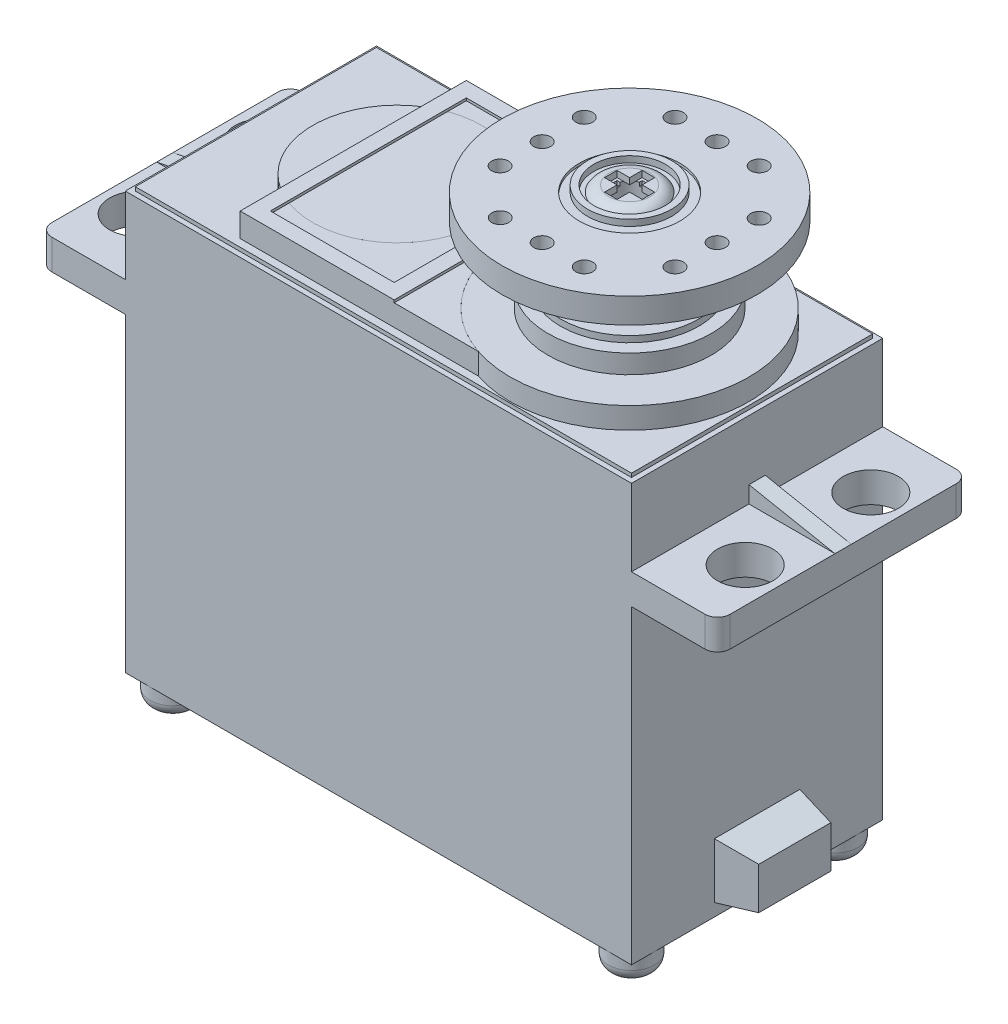
SolidWorks part; units mm, degrees
ref_plane "Alzado" through (0, 0, 0) normal (0, 0, 1) x (1, 0, 0)
ref_plane "Planta" through (0, 0, 0) normal (0, 1, 0) x (1, 0, 0)
ref_plane "Vista lateral" through (0, 0, 0) normal (1, 0, 0) x (0, 0, -1)
sketch "Croquis1" plane through (0, 0, 0) normal (0, 1, 0) x (1, 0, 0)
  line L1 (-20.15, 10) -> (20.15, 10)
  line L2 (-20.15, 10) -> (-20.15, -10)
  line L3 (-20.15, -10) -> (20.15, -10)
  line L4 (20.15, 10) -> (20.15, -10)
  line L5 (-20.15, 10) -> (20.15, -10) construction
  line L6 (-20.15, -10) -> (20.15, 10) construction
  point P0 (0, 0)
  dimension "D1" = 40.3
  dimension "D2" = 20
extrude "Saliente-Extruir1" add sketch "Croquis1" along normal blind 35.5
sketch "Croquis2" plane through (20.15, 0, 0) normal (1, 0, 0) x (0, 0, -1)
  line L0 (10, 35.5) -> (10, 26.7) construction
  line L1 (10, 35.5) -> (10, 0) construction
  line L2 (10, 26.7) -> (10, 29.1)
  line L3 (10, 29.1) -> (-10, 29.1)
  line L4 (-10, 35.5) -> (-10, 0) construction
  line L5 (-10, 29.1) -> (-10, 26.7)
  line L6 (-10, 26.7) -> (10, 26.7)
  dimension "D1" = 8.8
  dimension "D2" = 2.4
extrude "Saliente-Extruir2" add sketch "Croquis2" along normal blind 6.85
sketch "Croquis3" plane through (-20.15, 0, 0) normal (-1, 0, 0) x (0, 0, 1)
  line L0 (10, 35.5) -> (10, 26.7) construction
  line L1 (10, 35.5) -> (10, 0) construction
  line L2 (10, 26.7) -> (10, 29.1)
  line L3 (10, 29.1) -> (-10, 29.1)
  line L4 (-10, 35.5) -> (-10, 0) construction
  line L5 (-10, 29.1) -> (-10, 26.7)
  line L6 (-10, 26.7) -> (10, 26.7)
  dimension "D1" = 8.8
  dimension "D2" = 2.4
extrude "Saliente-Extruir3" add sketch "Croquis3" along normal blind 6.85
fillet "Redondeo1" radius 1 1 edges at (27, 27.9, 10) type face fillet first side face at (27, 27.9, 0) second side face at (0, 27.275, 10)
fillet "Redondeo2" radius 1 1 edges at (27, 27.9, -10) type face fillet first side face at (27, 27.9, -0.5) second side face at (0, 27.275, -10)
fillet "Redondeo3" radius 1 1 edges at (-27, 27.9, 10) type face fillet first side face at (-27, 27.9, 0) second side face at (-0.25, 27.275, 10)
fillet "Redondeo4" radius 1 1 edges at (-27, 27.9, -10) type face fillet first side face at (-27, 27.9, -0.5) second side face at (-0.25, 27.275, -10)
sketch "Croquis4" plane through (0, 29.1, 0) normal (0, 1, 0) x (1, 0, 0)
  line L0 (27, 0) -> (20.15, 0) construction
  line L1 (27, 9) -> (27, -9) construction
  line L2 (20.15, 10) -> (20.15, -10) construction
  line L3 (20.15, 0) -> (20.15, 0.65)
  line L4 (20.15, -10) -> (20.15, 10) construction
  line L5 (20.15, 0.65) -> (27, 0.65)
  line L6 (27, 0.65) -> (27, 0)
  line L7 (27, 0) -> (27, -0.65)
  line L8 (27, -0.65) -> (20.15, -0.65)
  line L9 (20.15, -0.65) -> (20.15, 0)
  dimension "D1" = 0.65
  dimension "D2" = 0.65
extrude "Saliente-Extruir4" add sketch "Croquis4" along normal blind 1.5
chamfer "Chaflán1" distance 1.5 angle 79 1 edges at (27, 30.6, 0) first distance on face at (27, 28.875, 0)
sketch "Croquis5" plane through (0, 29.1, 0) normal (0, 1, 0) x (1, 0, 0)
  line L0 (-27, 0) -> (-20.15, 0) construction
  line L1 (-27, -9) -> (-27, 9) construction
  line L2 (-20.15, 10) -> (-20.15, -10) construction
  line L3 (-27, 0) -> (-27, 0.65)
  line L4 (-27, 0.65) -> (-20.15, 0.65)
  line L5 (-20.15, -10) -> (-20.15, 10) construction
  line L6 (-20.15, 0.65) -> (-20.15, 0)
  line L7 (-20.15, 0) -> (-20.15, -0.65)
  line L8 (-20.15, -0.65) -> (-27, -0.65)
  line L9 (-27, -0.65) -> (-27, 0)
  dimension "D1" = 0.65
  dimension "D2" = 0.65
extrude "Saliente-Extruir5" add sketch "Croquis5" along normal blind 1.5
chamfer "Chaflán2" distance 1.5 angle 79 1 edges at (-27, 30.6, 0) first distance on face at (-27, 28.875, 0)
sketch "Croquis6" plane through (0, 29.1, 0) normal (0, 1, 0) x (1, 0, 0)
  line L0 (27, 0) -> (20.15, 0) construction
  line L1 (27, 0.65) -> (27, -0.65) construction
  line L2 (20.15, -10) -> (20.15, 10) construction
  line L3 (27.75, 10) -> (24.2, 10) construction
  line L4 (26, 10) -> (20.15, 10) construction
  line L5 (24.2, 10) -> (24.2, 5) construction
  line L6 (24.2, 5) -> (24.2, -5) construction
  line L7 (24.2, -5) -> (24.2, -10) construction
  line L8 (26, -10) -> (20.15, -10) construction
  line L9 (24.2, -10) -> (27.75, -10) construction
  circle A0 centre (24.2, 5) radius 2.2
  circle A1 centre (24.2, -5) radius 2.2
  dimension "D1" = 5
  dimension "D3" = 4.4
  dimension "D5" = 4.4
  dimension "D2" = 3.55
  dimension "D4" = 10
  dimension "D6" = 5
extrude "Cortar-Extruir1" cut sketch "Croquis6" against normal blind 2.6
sketch "Croquis7" plane through (0, 29.1, 0) normal (0, 1, 0) x (1, 0, 0)
  line L0 (-24.2, -10) -> (-27.75, -10) construction
  line L1 (-26, -10) -> (-20.15, -10) construction
  line L2 (-24.2, -10) -> (-24.2, -5) construction
  line L3 (-24.2, -5) -> (-24.2, 5) construction
  line L4 (-24.2, 5) -> (-24.2, 10) construction
  line L5 (-26, 10) -> (-20.15, 10) construction
  circle A0 centre (-24.2, -5) radius 2.2
  circle A1 centre (-24.2, 5) radius 2.2
  dimension "D3" = 4.4
  dimension "D4" = 10
  dimension "D6" = 4.4
  dimension "D1" = 5
  dimension "D2" = 3.55
  dimension "D5" = 5
extrude "Cortar-Extruir2" cut sketch "Croquis7" against normal blind 2.6
sketch "Croquis8" plane through (0, 35.5, 0) normal (0, 1, 0) x (1, 0, 0)
  line L0 (-20.15, 10) -> (-20.15, 9.6) construction
  line L1 (-20.15, 10) -> (-20.15, -10) construction
  line L2 (-20.15, 9.6) -> (-19.75, 9.6) construction
  line L3 (-20.15, -10) -> (-20.15, -9.6) construction
  line L4 (-20.15, -9.6) -> (-19.75, -9.6) construction
  line L5 (20.15, -9.6) -> (19.75, -9.6) construction
  line L6 (20.15, -10) -> (20.15, 10) construction
  line L7 (19.75, -9.6) -> (19.75, -10) construction
  line L8 (-20.15, -10) -> (20.15, -10) construction
  line L9 (20.15, 10) -> (20.15, 9.6) construction
  line L10 (20.15, 9.6) -> (19.75, 9.6) construction
  line L11 (19.75, 9.6) -> (19.75, 10) construction
  line L12 (20.15, 10) -> (-20.15, 10) construction
  line L13 (-20.15, 10) -> (-20.15, -10)
  line L14 (-20.15, -10) -> (20.15, -10)
  line L15 (20.15, -10) -> (20.15, 10)
  line L16 (20.15, 10) -> (-20.15, 10)
  line L17 (-19.75, 9.6) -> (-19.75, -9.6)
  line L18 (-19.75, -9.6) -> (19.75, -9.6)
  line L19 (19.75, -9.6) -> (19.75, 9.6)
  line L20 (19.75, 9.6) -> (-19.75, 9.6)
  dimension "D1" = 0.4
  dimension "D2" = 0.4
  dimension "D3" = 0.4
  dimension "D4" = 0.4
  dimension "D5" = 0.4
extrude "Cortar-Extruir3" cut sketch "Croquis8" against normal blind 0.3
sketch "Croquis9" plane through (0, 0, 0) normal (0, -1, 0) x (1, 0, 0)
  line L0 (-20.15, -10) -> (-16.35, -10)
  line L1 (-20.15, -10) -> (-20.15, -6.2)
  line L2 (-16.35, -10) -> (-16.35, -6.2)
  line L3 (-20.15, -6.2) -> (-16.35, -6.2)
  line L4 (20.15, -10) -> (-20.15, -10) construction
  line L5 (-20.15, 10) -> (-16.35, 10)
  line L6 (-20.15, 10) -> (-20.15, 6.2)
  line L7 (-16.35, 10) -> (-16.35, 6.2)
  line L8 (-20.15, 6.2) -> (-16.35, 6.2)
  line L9 (-20.15, 10) -> (20.15, 10) construction
  line L10 (20.15, 10) -> (20.15, 6.2)
  line L11 (20.15, 10) -> (16.35, 10)
  line L12 (20.15, 6.2) -> (16.35, 6.2)
  line L13 (16.35, 10) -> (16.35, 6.2)
  line L14 (20.15, 10) -> (20.15, -10) construction
  line L15 (20.15, -10) -> (20.15, -6.2)
  line L16 (20.15, -10) -> (16.35, -10)
  line L17 (20.15, -6.2) -> (16.35, -6.2)
  line L18 (16.35, -10) -> (16.35, -6.2)
  line L19 (20.15, 10) -> (20.15, -10) construction
  dimension "D1" = 3.8
  dimension "D2" = 3.8
  dimension "D3" = 3.8
  dimension "D4" = 3.8
  dimension "D5" = 3.8
  dimension "D6" = 3.8
  dimension "D7" = 3.8
  dimension "D8" = 3.8
extrude "Cortar-Extruir4" cut sketch "Croquis9" against normal blind 2
fillet "Redondeo5" radius 2 1 edges at (-16.35, 1, -6.2) type face fillet first side face at (-18.25, 1, -6.2) second side face at (-16.35, 1, -8.1)
fillet "Redondeo6" radius 2 1 edges at (-16.35, 1, 6.2) type face fillet first side face at (-16.35, 1, 8.1) second side face at (-18.25, 1, 6.2)
fillet "Redondeo7" radius 2 1 edges at (16.35, 1, 6.2) type face fillet first side face at (16.35, 1, 8.1) second side face at (18.25, 1, 6.2)
fillet "Redondeo8" radius 2 1 edges at (16.35, 1, -6.2) type face fillet first side face at (18.25, 1, -6.2) second side face at (16.35, 1, -8.1)
sketch "Croquis10" plane through (0, 2, 0) normal (0, -1, 0) x (1, 0, 0)
  line L0 (-20.15, -8.1) -> (20.15, -8.1) construction
  line L2 (-18.25, 10) -> (-18.25, -10) construction
  line L3 (-20.15, -6.2) -> (-20.15, -10) construction
  line L4 (20.15, 10) -> (20.15, -10) construction
  line L5 (-20.15, 8.1) -> (20.15, 8.1) construction
  line L6 (-20.15, 10) -> (-20.15, 6.2) construction
  line L7 (20.15, 6.2) -> (20.15, 10) construction
  line L8 (-16.35, 10) -> (-20.15, 10) construction
  line L9 (-20.15, -10) -> (-16.35, -10) construction
  line L10 (18.25, 10) -> (18.25, -10) construction
  line L11 (20.15, 10) -> (16.35, 10) construction
  line L12 (16.35, -10) -> (20.15, -10) construction
  line L13 (-18.25, 10) -> (-20.15, 10) construction
  line L14 (-20.15, 10) -> (-20.15, 8.1) construction
  line L15 (-20.15, 8.1) -> (-18.25, 8.1) construction
  line L16 (-20.15, -8.1) -> (-20.15, -10) construction
  line L17 (-20.15, -10) -> (-18.25, -10) construction
  line L18 (-18.25, -10) -> (-18.25, -8.1) construction
  line L19 (-18.25, -8.1) -> (-20.15, -8.1) construction
  line L20 (20.15, -8.1) -> (20.15, -10) construction
  line L21 (20.15, -10) -> (18.25, -10) construction
  line L22 (18.25, -10) -> (18.25, -8.1) construction
  line L23 (18.25, -8.1) -> (20.15, -8.1) construction
  line L24 (18.25, 10) -> (20.15, 10) construction
  line L25 (20.15, 10) -> (20.15, 8.1) construction
  line L26 (20.15, 8.1) -> (18.25, 8.1) construction
  line L27 (18.25, 8.1) -> (18.25, 10) construction
  circle A0 centre (-18.25, 8.1) radius 1.825
  circle A1 centre (-18.25, -8.1) radius 1.825
  circle A2 centre (18.25, -8.1) radius 1.825
  circle A3 centre (18.25, 8.1) radius 1.825
  dimension "D1" = 3.65
  dimension "D2" = 3.65
  dimension "D3" = 3.65
  dimension "D4" = 3.65
extrude "Saliente-Extruir6" add sketch "Croquis10" along normal blind 2
fillet "Redondeo9" radius 1 1 edges at (-18.25, 0, -9.925)
fillet "Redondeo10" radius 1 1 edges at (-18.25, 0, 6.275)
fillet "Redondeo11" radius 1 1 edges at (18.25, 0, -9.925)
fillet "Redondeo12" radius 1 1 edges at (18.25, 0, 6.275)
sketch "Croquis11" plane through (0, 0, 0) normal (0, -1, 0) x (1, 0, 0)
  line L0 (-18.25, -10) -> (-18.25, -8.1) construction
  line L1 (-20.15, -10) -> (-16.35, -10) construction
  line L2 (-18.25, -8.1) -> (-20.15, -8.1) construction
  line L3 (-20.15, -6.2) -> (-20.15, -10) construction
  line L4 (-18.25, 8.1) -> (-20.075, 8.1) construction
  line L5 (-18.75, -9.35) -> (-17.75, -9.35)
  line L6 (-18.75, -9.35) -> (-18.75, -8.6)
  line L7 (-18.75, -6.85) -> (-17.75, -6.85)
  line L8 (-17.75, -9.35) -> (-17.75, -8.6)
  line L9 (-18.75, -9.35) -> (-17.75, -6.85) construction
  line L10 (-18.75, -6.85) -> (-17.75, -9.35) construction
  line L11 (-19.5, -8.6) -> (-18.75, -8.6)
  line L12 (-19.5, -8.6) -> (-19.5, -7.6)
  line L13 (-19.5, -7.6) -> (-18.75, -7.6)
  line L14 (-17, -8.6) -> (-17, -7.6)
  line L15 (-19.5, -8.6) -> (-17, -7.6) construction
  line L16 (-19.5, -7.6) -> (-17, -8.6) construction
  line L17 (18.25, 8.1) -> (20.075, 8.1) construction
  line L18 (-18.75, 9.35) -> (-17.75, 9.35)
  line L19 (-18.75, 9.35) -> (-18.75, 8.6)
  line L20 (-18.75, 6.85) -> (-17.75, 6.85)
  line L21 (-17.75, 9.35) -> (-17.75, 8.6)
  line L22 (-18.75, 9.35) -> (-17.75, 6.85) construction
  line L23 (-18.75, 6.85) -> (-17.75, 9.35) construction
  line L24 (-17, 7.6) -> (-17.75, 7.6)
  line L25 (-17, 7.6) -> (-17, 8.6)
  line L26 (-17, 8.6) -> (-17.75, 8.6)
  line L27 (-19.5, 7.6) -> (-19.5, 8.6)
  line L28 (-17, 7.6) -> (-19.5, 8.6) construction
  line L29 (-17, 8.6) -> (-19.5, 7.6) construction
  line L30 (18.25, -8.1) -> (20.075, -8.1) construction
  line L31 (18.75, 6.85) -> (17.75, 6.85)
  line L32 (18.75, 6.85) -> (18.75, 7.6)
  line L33 (18.75, 9.35) -> (17.75, 9.35)
  line L34 (17.75, 6.85) -> (17.75, 7.6)
  line L35 (18.75, 6.85) -> (17.75, 9.35) construction
  line L36 (18.75, 9.35) -> (17.75, 6.85) construction
  line L37 (19.5, 7.6) -> (18.75, 7.6)
  line L38 (19.5, 7.6) -> (19.5, 8.6)
  line L39 (19.5, 8.6) -> (18.75, 8.6)
  line L40 (17, 7.6) -> (17, 8.6)
  line L41 (19.5, 7.6) -> (17, 8.6) construction
  line L42 (19.5, 8.6) -> (17, 7.6) construction
  line L43 (-17.75, -7.6) -> (-17, -7.6)
  line L44 (18.75, -6.85) -> (17.75, -6.85)
  line L45 (18.75, -6.85) -> (18.75, -7.6)
  line L46 (18.75, -9.35) -> (17.75, -9.35)
  line L47 (17.75, -6.85) -> (17.75, -7.6)
  line L48 (18.75, -6.85) -> (17.75, -9.35) construction
  line L49 (18.75, -9.35) -> (17.75, -6.85) construction
  line L50 (17, -8.6) -> (17.75, -8.6)
  line L51 (17, -8.6) -> (17, -7.6)
  line L52 (17, -7.6) -> (17.75, -7.6)
  line L53 (19.5, -8.6) -> (19.5, -7.6)
  line L54 (17, -8.6) -> (19.5, -7.6) construction
  line L55 (17, -7.6) -> (19.5, -8.6) construction
  line L56 (-18.75, -7.6) -> (-18.75, -6.85)
  line L57 (-18.75, 8.6) -> (-19.5, 8.6)
  line L58 (-17.75, -7.6) -> (-17.75, -6.85)
  line L59 (-17.75, -8.6) -> (-17, -8.6)
  line L60 (-17.75, 7.6) -> (-17.75, 6.85)
  line L61 (-18.75, 7.6) -> (-19.5, 7.6)
  line L62 (-18.75, 7.6) -> (-18.75, 6.85)
  line L63 (17.75, 8.6) -> (17, 8.6)
  line L64 (18.75, 8.6) -> (18.75, 9.35)
  line L65 (17.75, 7.6) -> (17, 7.6)
  line L66 (17.75, 8.6) -> (17.75, 9.35)
  line L67 (18.75, -7.6) -> (19.5, -7.6)
  line L68 (18.75, -8.6) -> (18.75, -9.35)
  line L69 (18.75, -8.6) -> (19.5, -8.6)
  line L70 (17.75, -8.6) -> (17.75, -9.35)
  circle A0 centre (-18.25, 8.1) radius 1.825 construction
  circle A1 centre (18.25, 8.1) radius 1.825 construction
  circle A2 centre (18.25, -8.1) radius 1.825 construction
  dimension "D1" = 2.5
  dimension "D2" = 2.5
  dimension "D3" = 1
  dimension "D4" = 1
  dimension "D5" = 1
  dimension "D6" = 1
  dimension "D7" = 2.5
  dimension "D8" = 2.5
  dimension "D9" = 1
  dimension "D10" = 1
  dimension "D11" = 2.5
  dimension "D12" = 2.5
  dimension "D13" = 1
  dimension "D14" = 1
  dimension "D15" = 2.5
  dimension "D16" = 2.5
extrude "Cortar-Extruir5" cut sketch "Croquis11" against normal blind 1
chamfer "Chaflán3" distance 2 angle 45 1 edges at (0, 0, -10)
chamfer "Chaflán4" distance 2 angle 45 1 edges at (20.15, 0, 0)
chamfer "Chaflán5" distance 2 angle 45 1 edges at (0, 0, 10)
chamfer "Chaflán6" distance 2 angle 45 1 edges at (-20.15, 0, 0)
sketch "Croquis12" plane through (0, 35.2, 0) normal (0, 1, 0) x (1, 0, 0)
  line L0 (0, 9.6) -> (0, 9) construction
  line L1 (0, 9) -> (-12, 9)
  line L2 (-12, 9) -> (-12, -9)
  line L3 (-12, -9) -> (0, -9)
  line L7 (19.75, 9.6) -> (-19.75, 9.6) construction
  line L8 (19.75, 0) -> (19.15, 0) construction
  line L11 (19.75, -9.6) -> (19.75, 9.6) construction
  line L12 (0, -9.6) -> (0, -9) construction
  line L13 (-19.75, -9.6) -> (19.75, -9.6) construction
  line L14 (-19.75, 0) -> (-19.15, 0) construction
  line L15 (-19.75, 9.6) -> (-19.75, -9.6) construction
  line L16 (0, 9) -> (19.15, 9) construction
  line L17 (19.15, 9) -> (19.15, 0) construction
  line L18 (19.15, 0) -> (19.15, -9) construction
  line L19 (19.15, -9) -> (0, -9) construction
  line L20 (0, -9) -> (-19.15, -9) construction
  line L22 (-19.15, -9) -> (-19.15, 0) construction
  line L23 (-19.15, 0) -> (-19.15, 9) construction
  line L24 (-19.15, 9) -> (0, 9) construction
  line L25 (0, -9) -> (10, -9)
  line L26 (10, -9) -> (10, 9)
  line L27 (10, 9) -> (0, 9)
  dimension "D3" = 0.6
  dimension "D1" = 0.6
  dimension "D5" = 10
  dimension "D2" = 0.6
  dimension "D4" = 0.6
  dimension "D6" = 12
extrude "Saliente-Extruir7" add sketch "Croquis12" along normal blind 2.0001
sketch "Croquis13" plane through (0, 37.2001, 0) normal (0, 1, 0) x (1, 0, 0)
  line L0 (20.15, 0) -> (10, 0) construction
  line L1 (20.15, -0.65) -> (20.15, 0.65) construction
  circle A0 centre (10, 0) radius 9.5
  dimension "D2" = 19
  dimension "D1" = 10.15
extrude "Saliente-Extruir8" add sketch "Croquis13" along normal blind 0.0001 and the other way blind 2
sketch "Croquis14" plane through (0, 37.2002, 0) normal (0, 1, 0) x (1, 0, 0)
  circle A0 centre (10, 0) radius 6.5
  dimension "D1" = 13
extrude "Saliente-Extruir9" add sketch "Croquis14" along normal blind 1.5
sketch "Croquis15" plane through (0, 38.7002, 0) normal (0, 1, 0) x (1, 0, 0)
  circle A0 centre (10, 0) radius 5.5
  dimension "D1" = 11
extrude "Saliente-Extruir10" add sketch "Croquis15" along normal blind 0.5
sketch "Croquis16" plane through (0, 39.2002, 0) normal (0, 1, 0) x (1, 0, 0)
  circle A0 centre (10, 0) radius 2.9
extrude "Saliente-Extruir11" add sketch "Croquis16" along normal blind 4
sketch "Croquis17" plane through (0, 43.2002, 0) normal (0, 1, 0) x (1, 0, 0)
  circle A0 centre (10, 0) radius 0.85
  dimension "D1" = 1.7
extrude "Cortar-Extruir6" cut sketch "Croquis17" against normal blind 4
sketch "Croquis18" plane through (20.15, 0, 0) normal (1, 0, 0) x (0, 0, -1)
  line L0 (0, 2) -> (0, 3) construction
  line L1 (-6.2, 2) -> (6.2, 2) construction
  line L2 (0, 3) -> (0, 5.2) construction
  line L4 (-3.4, 7.4) -> (3.4, 7.4)
  line L5 (-3.4, 7.4) -> (-3.4, 3)
  line L6 (-3.4, 3) -> (3.4, 3)
  line L7 (3.4, 7.4) -> (3.4, 3)
  line L8 (-3.4, 7.4) -> (3.4, 3) construction
  line L9 (-3.4, 3) -> (3.4, 7.4) construction
  dimension "D1" = 1
  dimension "D2" = 2.2
  dimension "D3" = 4.4
  dimension "D4" = 6.8
extrude "Saliente-Extruir12" add sketch "Croquis18" along normal blind 3
chamfer "Chaflán7" distance 3 angle 10 1 edges at (23.15, 7.4, 0) first distance on face at (21.65, 7.4, 0)
chamfer "Chaflán8" distance 3 angle 10 1 edges at (23.15, 3, 0) first distance on face at (21.65, 3, 0)
chamfer "Chaflán9" distance 3 angle 10 1 edges at (23.15, 5.2, -3.4) first distance on face at (21.65, 5.2, -3.4)
chamfer "Chaflán10" distance 3 angle 10 1 edges at (23.15, 5.2, 3.4) first distance on face at (21.65, 5.2, 3.4)
sketch "Croquis19" plane through (0, 37.2001, 0) normal (0, 1, 0) x (1, 0, 0)
  line L0 (-12, 0) -> (-8.5, 0) construction
  line L1 (-12, 9) -> (-12, -9) construction
  circle A0 centre (-8.5, 0) radius 6.7149
  dimension "D1" = 3.5
extrude "Saliente-Extruir13" add sketch "Croquis19" along normal blind 0.0001 and the other way blind 2
sketch "Croquis20" plane through (0, 37.2001, 0) normal (0, 1, 0) x (1, 0, 0)
  line L0 (0.2582, -7.8) -> (0.2582, -9)
  line L1 (-12, -9) -> (6.9586, -9) construction
  line L3 (6.9586, 9) -> (-12, 9) construction
  line L4 (-0.9418, 7.8) -> (-0.9418, -7.8)
  line L6 (-12, -9) -> (-12, -5.7306) construction
  line L8 (-12, 5.7306) -> (-12, 9) construction
  line L9 (-0.9418, 7.8) -> (-10.8, 7.8)
  line L10 (-10.8, 7.8) -> (-10.8, -7.8)
  line L11 (-10.8, -7.8) -> (-0.9418, -7.8)
  line L14 (-0.9418, 9) -> (0.2582, 9)
  line L15 (0.2582, 9) -> (0.2582, 7.8)
  line L16 (0.2582, 7.8) -> (0.2582, -7.8)
  line L17 (0.2582, -9) -> (-0.9418, -9)
  line L18 (-0.9418, -9) -> (-12, -9)
  line L19 (-12, -9) -> (-12, -7.8)
  line L20 (-12, -7.8) -> (-12, 7.8)
  line L21 (-12, 7.8) -> (-12, 9)
  line L22 (-12, 9) -> (-0.9418, 9)
extrude "Saliente-Extruir14" add sketch "Croquis20" along normal blind 0.2
sketch "Croquis21" plane through (0, 43.2002, 0) normal (0, 1, 0) x (1, 0, 0)
  circle A0 centre (10, 0) radius 4.3
  dimension "D1" = 8.6
extrude "Saliente-Extruir15" add sketch "Croquis21" along normal blind 2 and the other way blind 3
sketch "Croquis22" plane through (0, 45.2002, 0) normal (0, 1, 0) x (1, 0, 0)
  circle A0 centre (10, 0) radius 10.15
  dimension "D1" = 20.3
extrude "Saliente-Extruir16" add sketch "Croquis22" along normal blind 0.0001 and the other way blind 2
sketch "Croquis23" plane through (0, 45.2003, 0) normal (0, 1, 0) x (1, 0, 0)
  circle A0 centre (10, 0) radius 1.375
  dimension "D1" = 2.75
extrude "Cortar-Extruir7" cut sketch "Croquis23" against normal blind 5.2
sketch "Croquis24" plane through (0, 45.2003, 0) normal (0, 1, 0) x (1, 0, 0)
  circle A0 centre (10, 0) radius 2.85
  circle A1 centre (10, 0) radius 3.35
  dimension "D1" = 5.7
  dimension "D2" = 6.7
extrude "Saliente-Extruir17" add sketch "Croquis24" along normal blind 0.5
chamfer "Chaflán11" distance 0.75 angle 45 1 edges at (10, 40.2002, 4.3)
sketch "Croquis25" plane through (0, 45.2003, 0) normal (0, 1, 0) x (1, 0, 0)
  circle A0 centre (10, 0) radius 2.5
  dimension "D1" = 5
extrude "Saliente-Extruir18" add sketch "Croquis25" along normal blind 0.5
fillet "Redondeo13" radius 1 1 edges at (10, 45.7003, 2.5)
sketch "Croquis27" plane through (0, 45.7003, 0) normal (0, 1, 0) x (1, 0, 0)
  line L1 (9.5, -1.5) -> (10.5, -1.5)
  line L2 (9.5, -1.5) -> (9.5, 1.5)
  line L3 (9.5, 1.5) -> (10.5, 1.5)
  line L4 (10.5, -1.5) -> (10.5, 1.5)
  line L5 (9.5, -1.5) -> (10.5, 1.5) construction
  line L6 (9.5, 1.5) -> (10.5, -1.5) construction
  line L7 (8.5, 0.5) -> (11.5, 0.5)
  line L8 (8.5, 0.5) -> (8.5, -0.5)
  line L9 (8.5, -0.5) -> (11.5, -0.5)
  line L10 (11.5, 0.5) -> (11.5, -0.5)
  line L11 (8.5, 0.5) -> (11.5, -0.5) construction
  line L12 (8.5, -0.5) -> (11.5, 0.5) construction
  point P0 (10, 0)
  point P6 (10, 0)
  dimension "D1" = 3
  dimension "D2" = 3
  dimension "D3" = 1
  dimension "D4" = 1
extrude "Cortar-Extruir8" cut sketch "Croquis27" against normal blind 1 contours L2 L7 L4 L3 | L2 L9 L4 L7 | L9 L2 L1 L4 | L8 L9 L2 L7 | L10 L7 L4 L9 region at (10, 45.7003, 1) region at (9, 45.7003, 0) region at (10, 45.7003, 0) region at (11, 45.7003, 0) region at (10, 45.7003, -1)
sketch "Croquis28" plane through (0, 45.2003, 0) normal (0, 1, 0) x (1, 0, 0)
  circle A0 centre (10, 0) radius 4
extrude "Cortar-Extruir10" cut sketch "Croquis28" against normal blind 0.2
sketch "Croquis29" plane through (0, 45.2003, 0) normal (0, 1, 0) x (1, 0, 0)
  line L0 (10, 0) -> (10, 6.9625) construction
  line L1 (10, 0) -> (16.9625, 0) construction
  line L2 (10, 0) -> (10, -6.9625) construction
  line L3 (10, -10.15) -> (10.0213, -10.1229) construction
  line L4 (10, 0) -> (3.0375, 0) construction
  circle A0 centre (10, 0) radius 10.15 construction
  circle A1 centre (3.0375, 0) radius 0.675
  circle A2 centre (10, 6.9625) radius 0.675
  circle A3 centre (16.9625, 0) radius 0.675
  circle A4 centre (10, -6.9625) radius 0.675
  dimension "D4" = 1.35
  dimension "D5" = 1.35
  dimension "D6" = 1.35
  dimension "D7" = 1.35
  dimension "D1" = 6.9625
  dimension "D2" = 6.9625
  dimension "D3" = 6.9625
extrude "Cortar-Extruir11" cut sketch "Croquis29" against normal blind 2.5
sketch "Croquis30" plane through (0, 45.2003, 0) normal (0, 1, 0) x (1, 0, 0)
  line L0 (16.9625, 0) -> (16.9625, 3.35) construction
  line L1 (16.9625, 0) -> (16.9625, -3.35) construction
  line L2 (10, 6.9625) -> (13.35, 6.9625) construction
  line L3 (10, 6.9625) -> (6.65, 6.9625) construction
  line L4 (3.0375, 0) -> (3.0375, 3.35) construction
  line L5 (3.0375, 0) -> (3.0375, -3.35) construction
  line L6 (10, -6.9625) -> (13.35, -6.9625) construction
  line L7 (10, -6.9625) -> (6.65, -6.9625) construction
  line L8 (6.65, -6.9625) -> (6.6113, -6.9113) construction
  circle A1 centre (6.65, 6.9625) radius 0.675
  circle A2 centre (13.35, 6.9625) radius 0.675
  circle A3 centre (3.0375, 3.35) radius 0.675
  circle A4 centre (3.0375, -3.35) radius 0.675
  circle A5 centre (6.6113, -6.9113) radius 0.675
  circle A6 centre (13.35, -6.9625) radius 0.675
  circle A7 centre (16.9625, -3.35) radius 0.675
  circle A8 centre (16.9625, 3.35) radius 0.675
  dimension "D3" = 3.35
  dimension "D9" = 1.35
  dimension "D10" = 1.35
  dimension "D11" = 1.35
  dimension "D12" = 1.35
  dimension "D13" = 1.35
  dimension "D14" = 1.35
  dimension "D15" = 1.35
  dimension "D16" = 1.35
  dimension "D1" = 3.35
  dimension "D2" = 3.35
  dimension "D4" = 3.35
  dimension "D5" = 3.35
  dimension "D6" = 3.35
  dimension "D7" = 3.35
  dimension "D8" = 3.35
extrude "Cortar-Extruir12" cut sketch "Croquis30" against normal blind 2.5
